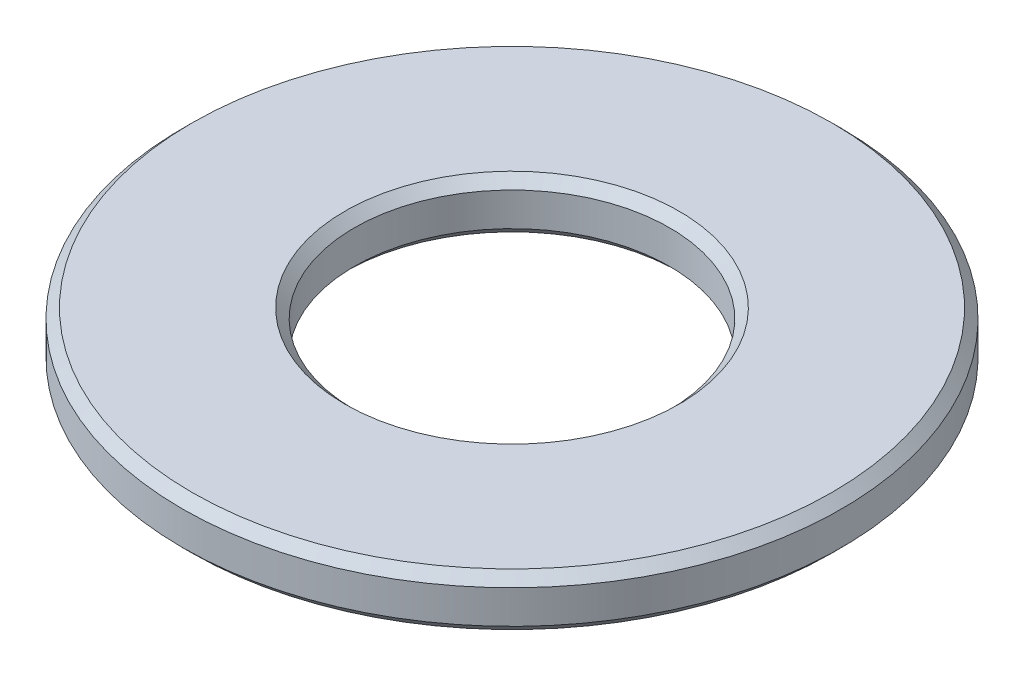
SolidWorks part; units mm, degrees
ref_plane "Ebene vorne" through (0, 0, 0) normal (0, 0, 1) x (1, 0, 0)
ref_plane "Ebene oben" through (0, 0, 0) normal (0, 1, 0) x (1, 0, 0)
ref_plane "Ebene rechts" through (0, 0, 0) normal (1, 0, 0) x (0, 0, -1)
sketch "Skizze1" plane through (0, 0, 0) normal (0, 1, 0) x (1, 0, 0)
  circle A0 centre (0, 0) radius 1.65
  circle A1 centre (0, 0) radius 3.45
  dimension "D1" = 3.3
  dimension "D2" = 6.9
extrude "Aufsatz-Linear austragen1" add sketch "Skizze1" along normal blind 0.55
ref_axis "Achse1" through (0, -0.0275, 0) along (0, 1, 0)
chamfer "Fase1" distance 0.1 angle 45 4 edges at (0, 0.55, 3.45) (0, 0, 3.45) (0, 0.55, 1.65) (0, 0, 1.65)
